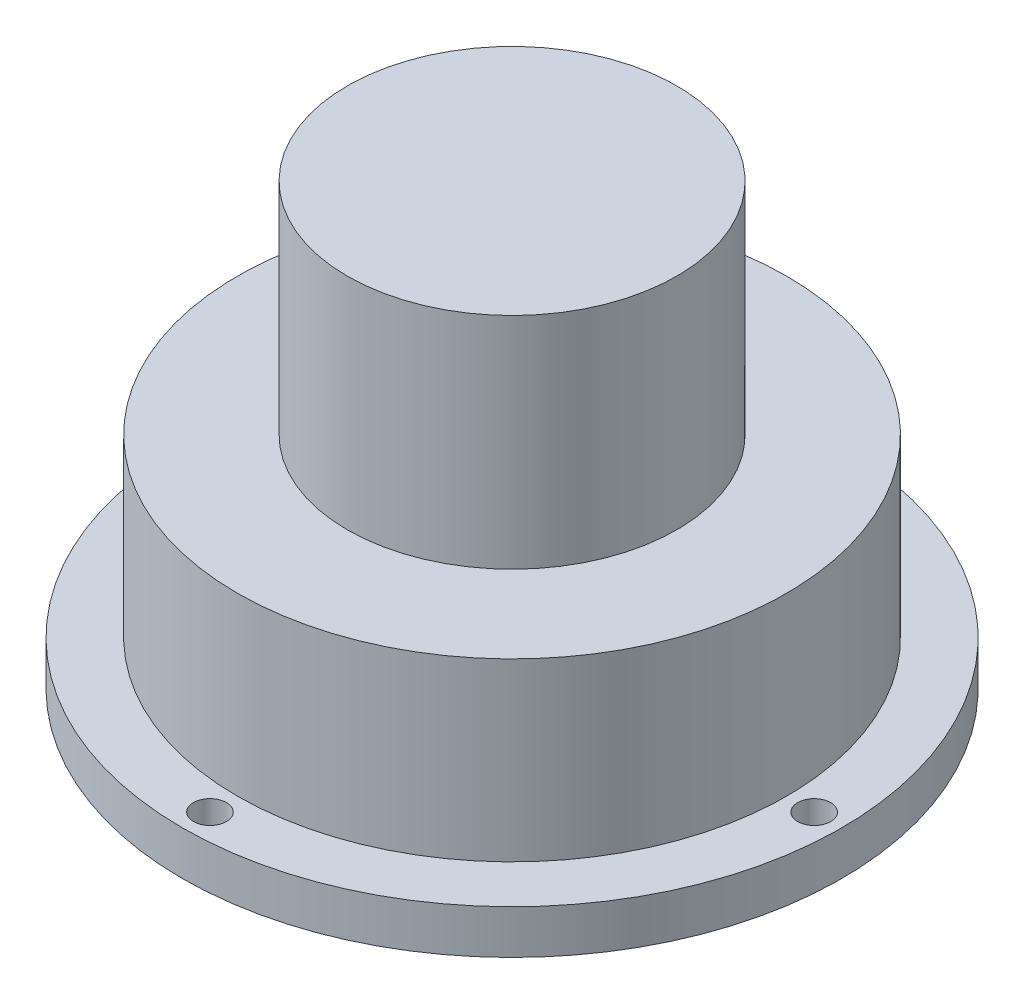
SolidWorks part; units mm, degrees
material "AISI 1020"
ref_plane "Front Plane" through (0, 0, 0) normal (0, 0, 1) x (1, 0, 0)
ref_plane "Top Plane" through (0, 0, 0) normal (0, 1, 0) x (1, 0, 0)
ref_plane "Right Plane" through (0, 0, 0) normal (1, 0, 0) x (0, 0, -1)
sketch "Sketch1" plane through (0, 0, 0) normal (0, 1, 0) x (1, 0, 0)
  circle A0 centre (0, 0) radius 125
  circle A1 centre (0, 0) radius 150
  dimension "D1" = 250
  dimension "D2" = 300
extrude "Boss-Extrude1" add sketch "Sketch1" along normal blind 20
extrude "Boss-Extrude2" add sketch "Sketch1<2>" along normal blind 100 contours A0
sketch "Sketch1<2>" plane through (0, 0, 0) normal (0, 1, 0) x (1, 0, 0) same geometry as "Sketch1"
sketch "Sketch2" plane through (0, 100, 0) normal (0, 1, 0) x (1, 0, 0)
  circle A0 centre (0, 0) radius 75
  dimension "D1" = 150
extrude "Boss-Extrude3" add sketch "Sketch2" along normal blind 100
sketch "Sketch3" plane through (0, 20, 0) normal (0, 1, 0) x (1, 0, 0)
  circle A0 centre (0, 0) radius 137.5 construction
  point P3 (137.5, 0)
  dimension "D1" = 275
hole_wizard "Ø15.0 (15) Diameter Hole1" positions "Sketch3" profile "Sketch4" hole size "Ø15.0" standard "ISO" end condition through all
sketch "Sketch4" plane through (137.5, 20, 0) normal (1, 0, 0) x (0, 0, 1)
  line L0 (0, 0) -> (0, 20)
  line L1 (0, 20) -> (7.5, 20)
  line L2 (7.5, 20) -> (7.5, 0)
  line L5 (7.5, 0) -> (0, 0)
  line L11 (0, -6.35) -> (0, 107.95) construction
  dimension "Thru Hole Dia." = 15
  dimension "Thru Hole Depth" = 20
pattern_circular "CirPattern1" count 4 over 360 about axis through (0, 100, 0) along (0, -1, 0) of "Ø15.0 (15) Diameter Hole1"
